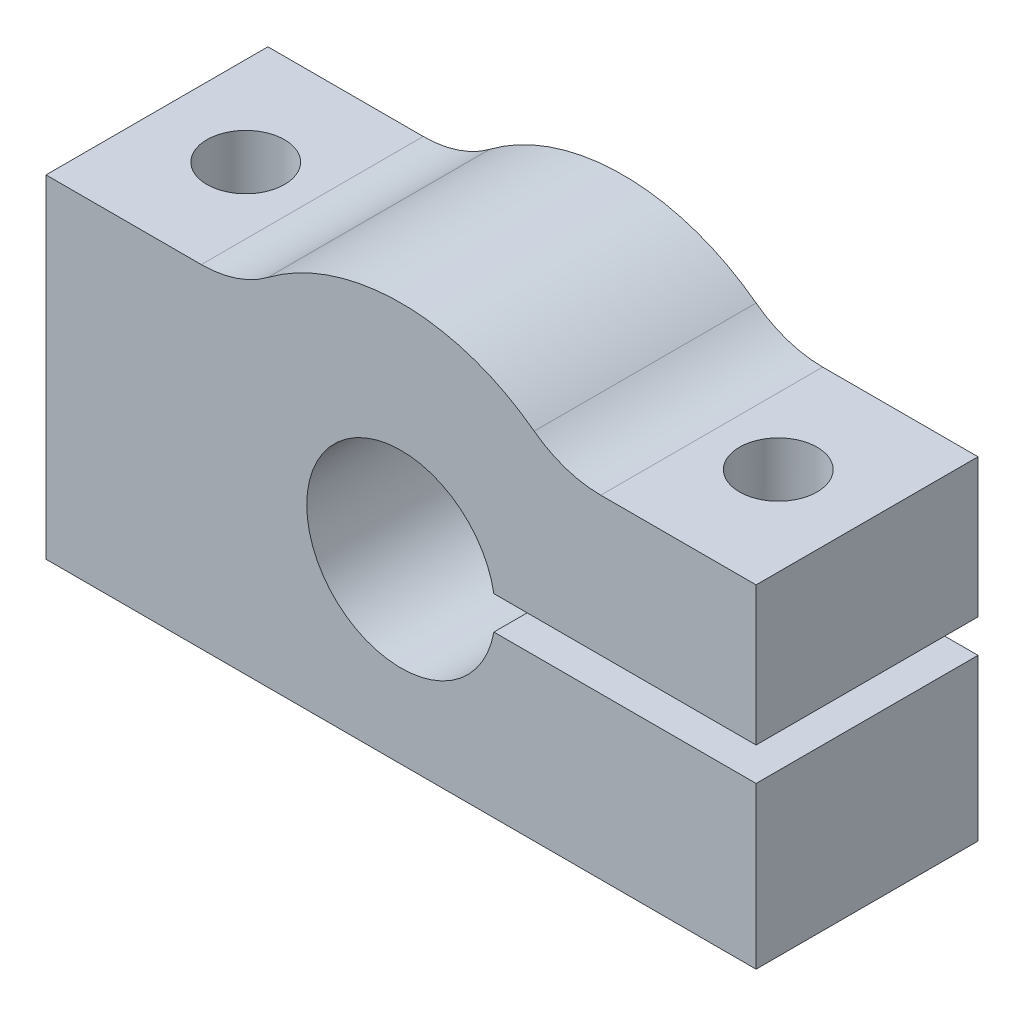
SolidWorks part; units mm, degrees
ref_plane "Alzado" through (0, 0, 0) normal (0, 0, 1) x (1, 0, 0)
ref_plane "Planta" through (0, 0, 0) normal (0, 1, 0) x (1, 0, 0)
ref_plane "Vista lateral" through (0, 0, 0) normal (1, 0, 0) x (0, 0, -1)
sketch "Croquis1" plane through (0, 0, 0) normal (0, 0, 1) x (1, 0, 0)
  line L0 (0, -55) -> (0, 55) construction
  line L1 (55, 0) -> (-55, 0) construction
  line L2 (4.1833, 8.75) -> (16, 8.75)
  line L3 (-16, 0) -> (16, 0)
  line L4 (-16, 0) -> (-16, 15)
  line L5 (4.1833, 7.25) -> (16, 7.25)
  line L6 (16, 0) -> (16, 7.25)
  line L7 (0, 8) -> (15.2017, 8) construction
  line L8 (16, 8.75) -> (16, 15)
  line L9 (0, 0) -> (0, 32.3406) construction
  line L10 (-16, 15) -> (-7.1414, 15)
  line L11 (7.1414, 15) -> (16, 15)
  arc A0 (4.1833, 8.75) -> (4.1833, 7.25) centre (0, 8) ccw
  arc A2 (7.1414, 15) -> (-7.1414, 15) centre (0, 8) ccw
  dimension "D1" = 8.5
  dimension "D3" = 1.5
  dimension "D5" = 32
  dimension "D7" = 10
  dimension "D2" = 8
  dimension "D4" = 32
  dimension "D6" = 15
extrude "Saliente-Extruir1" add sketch "Croquis1" along normal blind 5 and the other way blind 5
sketch "Croquis6" plane through (0, 0, 0) normal (0, -1, 0) x (1, 0, 0)
  line L0 (55, 0) -> (-55, 0) construction
  line L1 (-16, -5) -> (-16, 5) construction
  line L2 (16, -5) -> (16, 5) construction
  circle A0 centre (-12, 0) radius 1.75
  circle A1 centre (12, 0) radius 1.75
  dimension "D1" = 3.5
  dimension "D2" = 4
  dimension "D3" = 4
extrude "Cortar-Extruir4" cut sketch "Croquis6" against normal through all
fillet "Redondeo1" radius 5 2 edges at (-7.1414, 15, 0) (7.1414, 15, 0)
